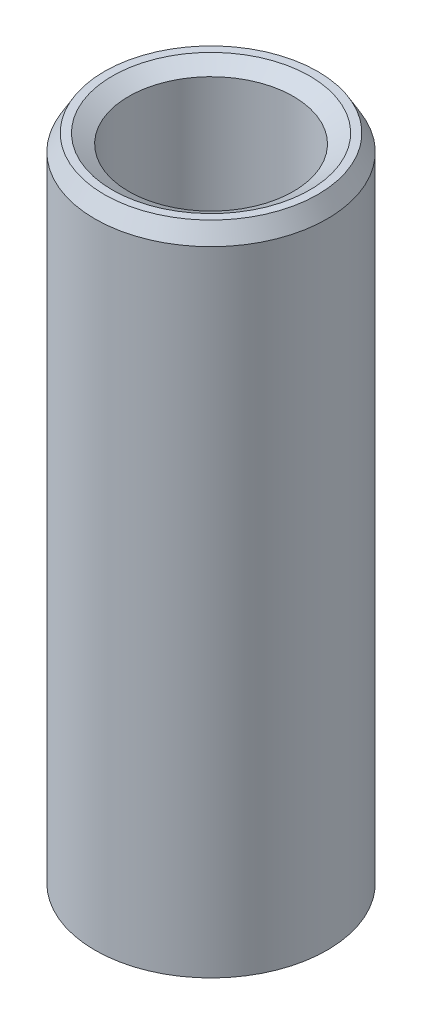
SolidWorks part; units mm, degrees
ref_plane "Front Plane" through (0, 0, 0) normal (0, 0, 1) x (1, 0, 0)
ref_plane "Top Plane" through (0, 0, 0) normal (0, 1, 0) x (1, 0, 0)
ref_plane "Right Plane" through (0, 0, 0) normal (1, 0, 0) x (0, 0, -1)
sketch "Sketch1" plane through (0, 0, 0) normal (0, 1, 0) x (1, 0, 0)
  circle A0 centre (0, 0) radius 15
  dimension "SLEEVE_OD" = 30
extrude "Boss-Extrude1" add sketch "Sketch1" along normal blind 85.1324
sketch "Sketch2" plane through (0, 0, 0) normal (0, 1, 0) x (1, 0, 0)
  circle A0 centre (0, 0) radius 10.638
  dimension "BORE_D" = 21.276
extrude "Cut-Extrude1" cut sketch "Sketch2" along normal through all
chamfer "Chamfer1" distance 2.1145 angle 30 4 edges at (0, 85.1324, 10.638) (0, 0, 10.638) (0, 0, 15) (0, 85.1324, 15) first distance on face at (0, 85.1324, 10.638) first distance on face at (0, 0, 10.638) first distance on face at (0, 85.1324, 15)
